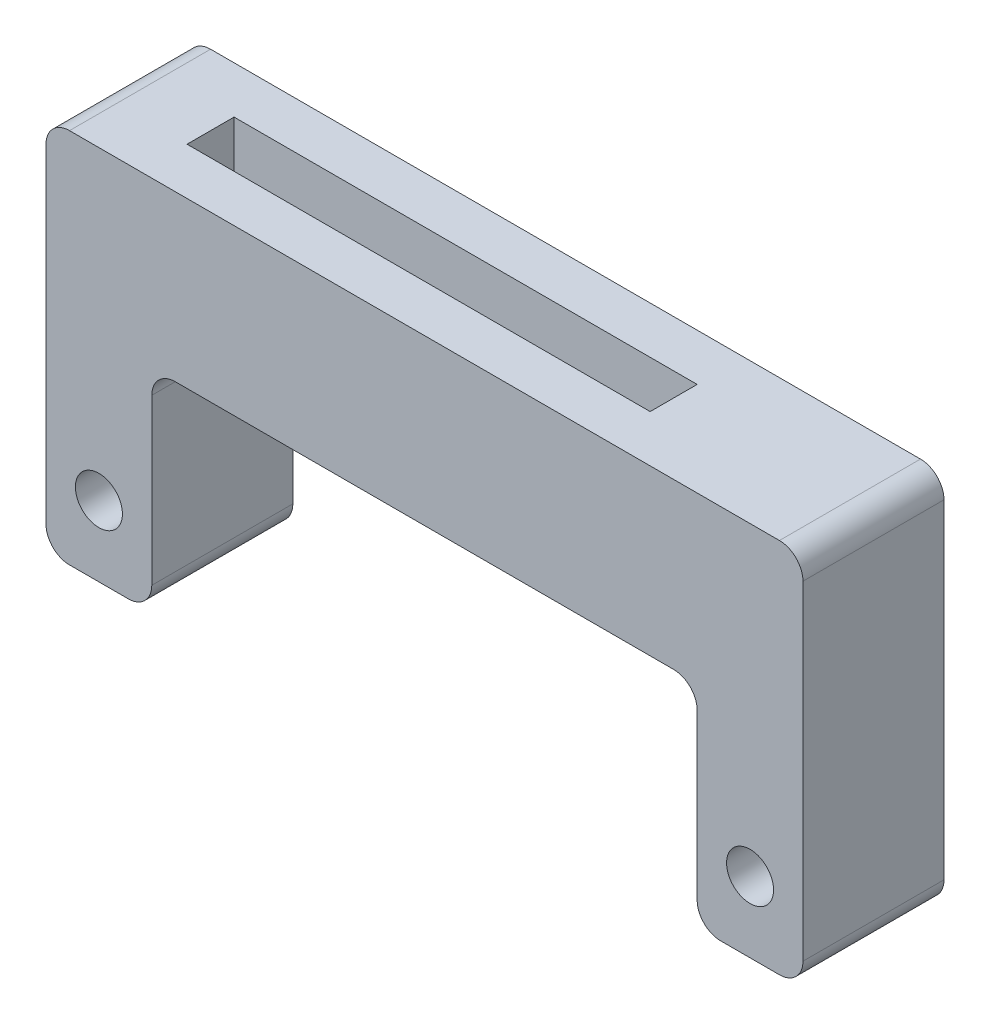
SolidWorks part; units mm, degrees
ref_plane "Front Plane" through (0, 0, 0) normal (0, 0, 1) x (1, 0, 0)
ref_plane "Top Plane" through (0, 0, 0) normal (0, 1, 0) x (1, 0, 0)
ref_plane "Right Plane" through (0, 0, 0) normal (1, 0, 0) x (0, 0, -1)
sketch "Sketch2" plane through (0, 0, 0) normal (0, 0, 1) x (1, 0, 0)
  line L1 (-16.1, -8) -> (16.1, -8)
  line L2 (-16.1, -8) -> (-16.1, 8)
  line L3 (-16.1, 8) -> (16.1, 8)
  line L4 (16.1, -8) -> (16.1, 8)
  line L5 (-16.1, -8) -> (16.1, 8) construction
  line L6 (-16.1, 8) -> (16.1, -8) construction
  point P0 (0, 0)
  dimension "D1" = 16
  dimension "D2" = 32.2
extrude "Boss-Extrude1" add sketch "Sketch2" along normal mid plane 6
sketch "Sketch3" plane through (0, 8, 0) normal (0, 1, 0) x (1, 0, 0)
  line L0 (-16.1, -3) -> (-16.1, 3) construction
  line L1 (-12.1, 1) -> (7.6, 1)
  line L2 (-12.1, 1) -> (-12.1, -1)
  line L3 (-12.1, -1) -> (7.6, -1)
  line L4 (7.6, 1) -> (7.6, -1)
  line L5 (16.1, -3) -> (16.1, 3) construction
  line L6 (16.1, 3) -> (-16.1, 3) construction
  dimension "D1" = 2
  dimension "D2" = 4
  dimension "D3" = 8.5
  dimension "D4" = 2
extrude "Cut-Extrude1" cut sketch "Sketch3" against normal blind 4
sketch "Sketch4" plane through (0, 0, 3) normal (0, 0, 1) x (1, 0, 0)
  line L0 (-16.1, -8) -> (16.1, -8) construction
  line L1 (-11.6, -8) -> (11.6, -8)
  line L2 (-11.6, -8) -> (-11.6, 1)
  line L3 (-11.6, 1) -> (11.6, 1)
  line L4 (11.6, -8) -> (11.6, 1)
  line L5 (-16.1, 8) -> (-16.1, -8) construction
  line L6 (16.1, -8) -> (16.1, 8) construction
  dimension "D1" = 9
  dimension "D2" = 4.5
  dimension "D3" = 4.5
extrude "Cut-Extrude2" cut sketch "Sketch4" against normal through all
sketch "Sketch5" plane through (0, 0, 3) normal (0, 0, 1) x (1, 0, 0)
  line L0 (-16.1, 8) -> (-16.1, -8) construction
  line L1 (16.1, -8) -> (16.1, 8) construction
  line L2 (-16.1, -8) -> (-11.6, -8) construction
  circle A0 centre (-13.85, -5) radius 1
  circle A2 centre (13.85, -5) radius 1
  dimension "D1" = 2
  dimension "D2" = 2.25
  dimension "D3" = 2.25
  dimension "D4" = 3
extrude "Cut-Extrude3" cut sketch "Sketch5" against normal through all
fillet "Fillet1" radius 1 8 edges at (16.1, 8, 0) (16.1, -8, 0) (11.6, -8, 0) (11.6, 1, 0) (-11.6, 1, 0) (-11.6, -8, 0) (-16.1, -8, 0) (-16.1, 8, 0)
